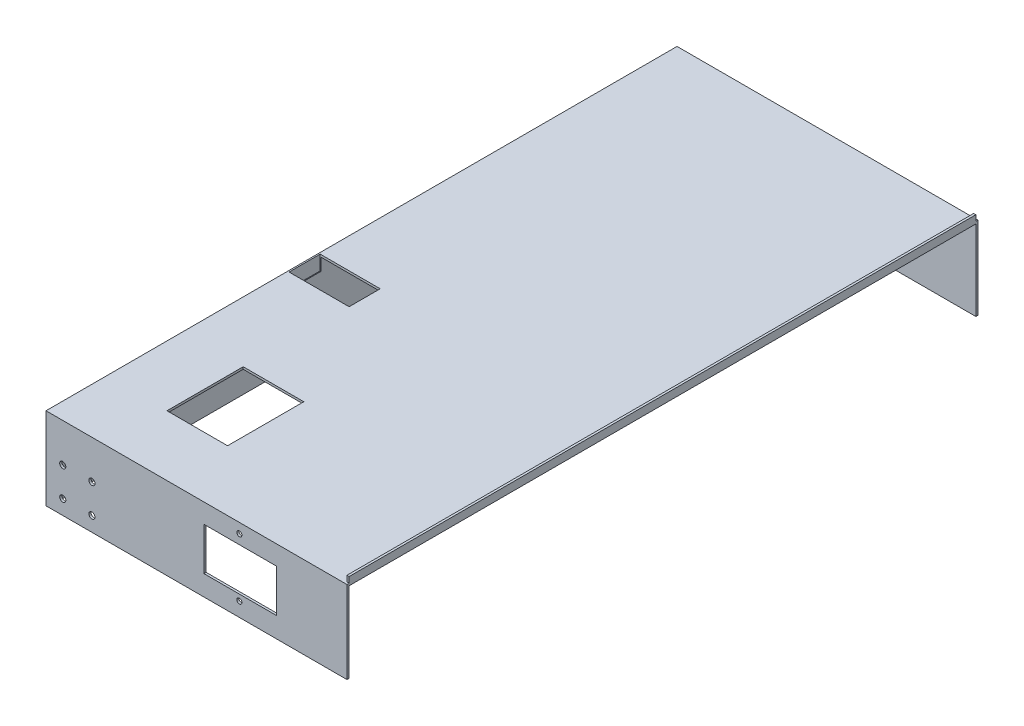
SolidWorks part; units mm, degrees
ref_plane "Front Plane" through (0, 0, 0) normal (0, 0, 1) x (1, 0, 0)
ref_plane "Top Plane" through (0, 0, 0) normal (0, 1, 0) x (1, 0, 0)
ref_plane "Right Plane" through (0, 0, 0) normal (1, 0, 0) x (0, 0, -1)
sketch "Sketch4" plane through (0, 0, 0) normal (0, 1, 0) x (1, 0, 0)
  line L0 (139.3737, 430) -> (344.3737, 430)
  line L1 (344.3737, 430) -> (344.3737, 0)
  line L2 (344.3737, 0) -> (139.3737, 0)
  line L3 (139.3737, 0) -> (139.3737, 65)
  line L7 (139.3737, 230) -> (139.3737, 430)
  line L8 (139.3737, 230) -> (139.3737, 65)
  line L10 (179.3737, 40) -> (220.958, 40)
  line L11 (179.3737, 40) -> (179.3737, 92.3012)
  line L12 (179.3737, 92.3012) -> (220.958, 92.3012)
  line L13 (220.958, 40) -> (220.958, 92.3012)
  point P12 (0, 0)
  point P13 (186.8851, 44.3419)
  point P14 (179.3737, 75.1255)
  point P15 (179.3737, 40)
  dimension "D2" = 200
  dimension "D5" = 205
  dimension "D6" = 205
extrude "Boss-Extrude4" add sketch "Sketch4" along normal blind 1.5 separate body
sketch "Sketch5" plane through (0, 0, 0) normal (0, 0, 1) x (1, 0, 0)
  line L1 (139.3737, 1.5) -> (344.3737, 1.5)
  line L2 (139.3737, 1.5) -> (139.3737, -55)
  line L3 (139.3737, -55) -> (344.3737, -55)
  line L4 (344.3737, 1.5) -> (344.3737, -55)
  dimension "D1" = 56.5
sketch "Sketch7" plane through (0, 0, -430) normal (0, 0, -1) x (-1, 0, 0)
  line L1 (-139.3737, 1.5) -> (-344.3737, 1.5)
  line L2 (-139.3737, 1.5) -> (-139.3737, -55)
  line L3 (-139.3737, -55) -> (-344.3737, -55)
  line L4 (-344.3737, 1.5) -> (-344.3737, -55)
  dimension "D1" = 56.5
sketch "Sketch8" plane through (0, 1.5, 0) normal (0, 1, 0) x (1, 0, 0)
  line L0 (139.3737, 430) -> (344.3737, 430) construction
  line L1 (344.3737, 0) -> (342.8737, 0)
  line L2 (344.3737, 0) -> (344.3737, 430)
  line L3 (344.3737, 430) -> (342.8737, 430)
  line L4 (342.8737, 0) -> (342.8737, 430)
  dimension "D1" = 1.5
extrude "Boss-Extrude5" add sketch "Sketch5" along normal blind 1.5
extrude "Boss-Extrude14" add sketch "Sketch8" along normal blind 4
extrude "Boss-Extrude18" add sketch "Sketch7" along normal blind 1.5
sketch "Sketch9" plane through (139.3737, 0, 0) normal (-1, 0, 0) x (0, 0, 1)
  line L1 (-431.5, 1.5) -> (1.5, 1.5)
  line L2 (-431.5, 1.5) -> (-431.5, -55)
  line L3 (-431.5, -55) -> (1.5, -55)
  line L4 (1.5, 1.5) -> (1.5, -55)
extrude "Boss-Extrude19" add sketch "Sketch9" along normal blind 1.5
sketch "Sketch10" plane through (0, 0, 1.5) normal (0, 0, 1) x (1, 0, 0)
  circle A0 centre (169.3737, -45) radius 2.1
  point P3 (0, 0)
  point P4 (169.3737, -45)
sketch "Sketch11" plane through (0, 0, 1.5) normal (0, 0, 1) x (1, 0, 0)
  circle A0 centre (149.3737, -45) radius 2.1
  point P3 (199.3737, -45)
  point P4 (199.3737, -45)
  point P5 (149.3737, -45)
sketch "Sketch12" plane through (0, 0, 1.5) normal (0, 0, 1) x (1, 0, 0)
  circle A0 centre (149.3737, -25) radius 2.1
  point P3 (0, 0)
  point P4 (159.7667, -27.1249)
  point P5 (149.3737, -25)
sketch "Sketch14" plane through (0, 0, 1.5) normal (0, 0, 1) x (1, 0, 0)
  circle A0 centre (169.3737, -25) radius 2.1
  point P3 (0, 0)
  point P4 (169.4098, -25.0305)
  point P5 (169.3737, -25)
sketch "Sketch15" plane through (0, 0, -431.5) normal (0, 0, -1) x (-1, 0, 0)
  circle A0 centre (-169.3737, -25) radius 2.1
  circle A1 centre (-149.3737, -25) radius 2.1
  circle A2 centre (-169.3737, -45) radius 2.1
  circle A3 centre (-149.3737, -45) radius 2.1
extrude "Cut-Extrude1" cut sketch "Sketch15" against normal blind 10
extrude "Cut-Extrude2" cut sketch "Sketch14" against normal blind 10
extrude "Cut-Extrude3" cut sketch "Sketch12" against normal blind 10
extrude "Cut-Extrude4" cut sketch "Sketch10" against normal blind 10
extrude "Cut-Extrude5" cut sketch "Sketch11" against normal blind 10
sketch "Sketch17" plane through (0, 1.5, 0) normal (0, 1, 0) x (1, 0, 0)
  line L1 (138.8371, 185.641) -> (180.0505, 185.641)
  line L2 (138.8371, 185.641) -> (138.8371, 164.3117)
  line L3 (138.8371, 164.3117) -> (180.0505, 164.3117)
  line L4 (180.0505, 185.641) -> (180.0505, 164.3117)
extrude "Cut-Extrude6" cut sketch "Sketch17" against normal blind 10
sketch "Sketch18" plane through (0, 0, 1.5) normal (0, 0, 1) x (1, 0, 0)
  line L1 (246.3048, -11.7715) -> (295.8862, -11.7715)
  line L2 (246.3048, -11.7715) -> (246.3048, -41.091)
  line L3 (246.3048, -41.091) -> (295.8862, -41.091)
  line L4 (295.8862, -11.7715) -> (295.8862, -41.091)
sketch "Sketch19" plane through (0, 0, 1.5) normal (0, 0, 1) x (1, 0, 0)
  circle A0 centre (270.5434, -5.2715) radius 1.75
  circle A1 centre (270.5434, -45.2715) radius 1.75
  point P6 (0, 0)
  point P7 (270.5434, -5.2715)
  point P8 (0, 0)
  point P9 (270.5434, -45.2715)
extrude "Cut-Extrude7" cut sketch "Sketch18" against normal blind 10
extrude "Cut-Extrude8" cut sketch "Sketch19" against normal blind 10
